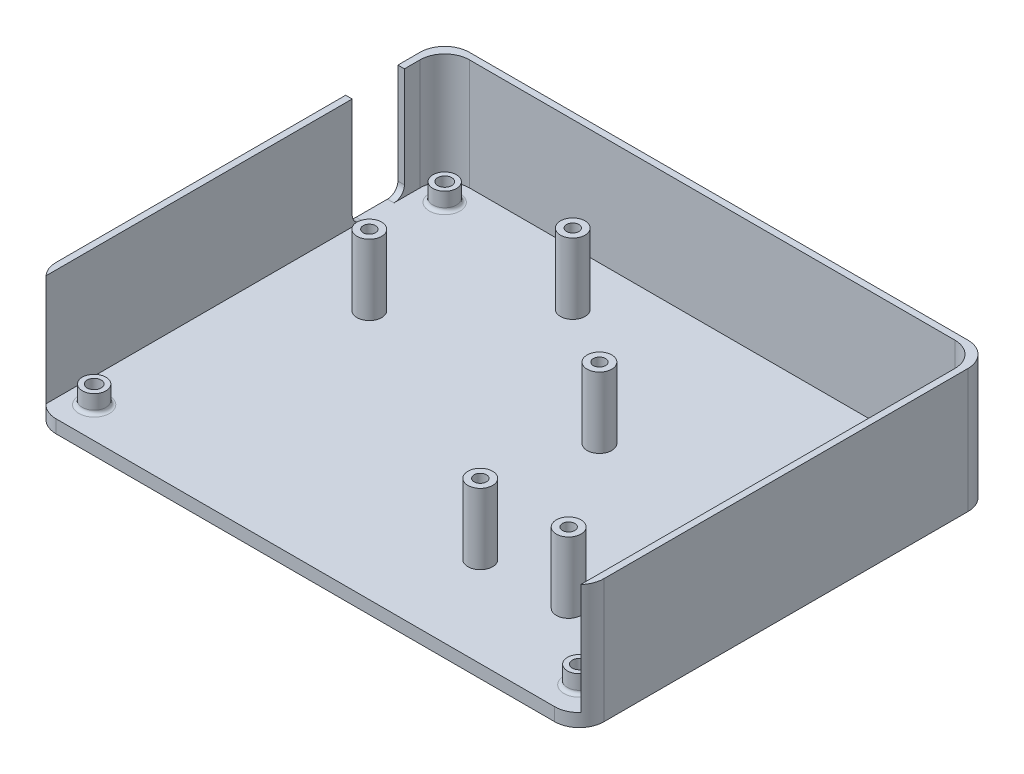
SolidWorks part; units mm, degrees
ref_plane "Front Plane" through (0, 0, 0) normal (0, 0, 1) x (1, 0, 0)
ref_plane "Top Plane" through (0, 0, 0) normal (0, 1, 0) x (1, 0, 0)
ref_plane "Right Plane" through (0, 0, 0) normal (1, 0, 0) x (0, 0, -1)
sketch "Sketch1" plane through (0, 0, 0) normal (0, 1, 0) x (1, 0, 0)
  line L0 (-66.8583, -50.2762) -> (-65.2708, -50.2762)
  line L1 (-65.2708, -50.2762) -> (64.8554, -50.2762)
  line L2 (-66.8583, -50.2762) -> (-66.8583, 44.2663)
  line L3 (-60.8583, 50.2663) -> (60.4429, 50.2663)
  line L4 (66.4429, -50.2762) -> (66.4429, 44.2663)
  line L5 (66.4429, -50.2762) -> (64.8554, -50.2762)
  line L6 (-50.3864, 41.1329) -> (-50.3864, 5.0649)
  line L7 (-50.3483, 41.1463) -> (49.9329, 41.1463)
  line L8 (-65.2708, -50.2762) -> (-65.2708, 42.6788)
  line L9 (-59.2708, 48.6788) -> (58.8554, 48.6788)
  line L10 (64.8554, -50.2762) -> (64.8554, 42.6788)
  line L11 (-50.3483, 41.1463) -> (-50.3483, -40.1162)
  line L12 (-50.3483, -40.1162) -> (49.9329, -40.1162)
  line L13 (49.9329, 41.1463) -> (49.9329, -40.1162)
  line L14 (-50.3864, 5.0649) -> (14.3836, 5.0649)
  line L15 (14.3836, 5.0649) -> (14.3836, -33.7971)
  line L16 (14.3836, -33.7971) -> (47.4036, -33.7971)
  line L17 (47.4036, -33.7971) -> (47.4036, 41.1329)
  line L18 (47.4036, 41.1329) -> (-50.3864, 41.1329)
  circle A0 centre (-59.2383, 42.6463) radius 1.7
  circle A1 centre (-59.2383, 42.6463) radius 2.875
  circle A2 centre (58.8229, 42.6463) radius 2.875
  circle A3 centre (58.8229, 42.6463) radius 1.7
  circle A4 centre (-59.2383, -42.6562) radius 2.875
  circle A5 centre (-59.2383, -42.6562) radius 1.7
  circle A6 centre (58.8229, -42.6562) radius 2.875
  circle A7 centre (58.8229, -42.6562) radius 1.7
  circle A8 centre (-21.0872, 35.6529) radius 1.5
  circle A9 centre (20.4128, -28.3471) radius 1.5
  circle A10 centre (-45.5872, 10.6529) radius 1.5
  circle A11 centre (10.4128, 10.6529) radius 1.5
  circle A12 centre (41.4128, -27.8471) radius 1.5
  arc A13 (-66.8583, 44.2663) -> (-60.8583, 50.2663) centre (-60.8583, 44.2663) cw
  arc A14 (-65.2708, 42.6788) -> (-59.2708, 48.6788) centre (-59.2708, 42.6788) cw
  circle A15 centre (-48.0512, -37.8237) radius 2
  arc A16 (58.8554, 48.6788) -> (64.8554, 42.6788) centre (58.8554, 42.6788) cw
  arc A17 (60.4429, 50.2663) -> (66.4429, 44.2663) centre (60.4429, 44.2663) cw
  circle A18 centre (-45.5872, 10.6529) radius 3
  circle A19 centre (-21.0872, 35.6529) radius 3
  circle A20 centre (10.4128, 10.6529) radius 3
  circle A21 centre (20.4128, -28.3471) radius 3
  circle A22 centre (41.4128, -27.8471) radius 3
  point P0 (0, 0)
  point P44 (-66.8583, 50.2663)
  point P53 (66.4429, 50.2663)
  dimension "D5" = 7.62
  dimension "D7" = 7.62
  dimension "D18" = 97.79
  dimension "D20" = 64.77
  dimension "D26" = 24.5
  dimension "D32" = 6
  dimension "D33" = 6
  dimension "D34" = 6
  dimension "D1" = 133.3013
  dimension "D2" = 100.5425
  dimension "D3" = 1.5875
  dimension "D4" = 1.5875
  dimension "D6" = 7.62
  dimension "D8" = 7.62
  dimension "D9" = 7.62
  dimension "D10" = 7.62
  dimension "D11" = 7.62
  dimension "D12" = 7.62
  dimension "D13" = 1.5875
  dimension "D14" = 9.12
  dimension "D15" = 16.51
  dimension "D16" = 16.51
  dimension "D17" = 81.2625
  dimension "D19" = 36.068
  dimension "D21" = 74.93
  dimension "D22" = 5.588
  dimension "D23" = 5.588
  dimension "D24" = 7.366
  dimension "D25" = 56
  dimension "D27" = 25
  dimension "D28" = 10
  dimension "D29" = 21
  dimension "D30" = 39
  dimension "D31" = 0.5
extrude "Boss-Extrude12" add sketch "Sketch1" along normal blind 3.175 contours L5 L4 A17 L3 A13 L2 L0 L1
extrude "Boss-Extrude13" add sketch "Sketch1<23>" along normal blind 30.1625 contours L10 L5 L4 L3 L2 L0 L8 L9 region at (-66.6913, 0, 3.005)
sketch "Sketch1<23>" plane through (0, 0, 0) normal (0, 1, 0) x (1, 0, 0) same geometry as "Sketch1"
extrude "Boss-Extrude15" add sketch "Sketch1<25>" along normal blind 7.525 contours A1 A0 | A2 A3 | A6 A7 | A4 A5 region at (-62.032, 0, -42.6463) region at (56.0293, 0, -42.6463) region at (-62.032, 0, 42.6562) region at (56.0293, 0, 42.6562)
sketch "Sketch1<25>" plane through (0, 0, 0) normal (0, 1, 0) x (1, 0, 0) same geometry as "Sketch1"
extrude "Cut-Extrude3" cut sketch "Sketch1<27>" along normal blind 28.575 contours A5 | A5 | A0 | A3 | A7 region at (-59.2383, 0, 42.6562)
sketch "Sketch1<27>" plane through (0, 0, 0) normal (0, 1, 0) x (1, 0, 0) same geometry as "Sketch1"
chamfer "Chamfer2" distance 1.45 angle 45 4 edges at (58.8229, 0, 44.3562) (58.8229, 0, -40.9463) (-59.2383, 0, 44.3562) (-59.2383, 0, -40.9463)
fillet "Fillet3" radius 6 2 edges at (66.4429, 15.0812, 50.2762) (-66.8583, 15.0812, 50.2762)
fillet "Fillet4" radius 0.85 1 edges at (-59.2383, 3.175, -45.5213)
fillet "Fillet5" radius 0.85 3 edges at (-59.2383, 3.175, 39.7812) (58.8229, 3.175, 39.7812) (58.8229, 3.175, -45.5213)
sketch "Sketch2" plane through (-65.2708, 0, 0) normal (1, 0, 0) x (0, 0, -1)
  line L0 (-48.3419, 3.175) -> (42.6788, 3.175) construction
  line L1 (38.8698, 3.175) -> (26.1698, 3.175)
  line L2 (38.8698, 3.175) -> (38.8698, 30.1625)
  line L3 (38.8698, 30.1625) -> (26.1698, 30.1625)
  line L4 (26.1698, 3.175) -> (26.1698, 30.1625)
  line L5 (-48.3419, 30.1625) -> (42.6788, 30.1625) construction
  line L6 (42.6788, 30.1625) -> (42.6788, 3.175) construction
  dimension "D1" = 12.7
  dimension "D2" = 3.8089
extrude "Cut-Extrude4" cut sketch "Sketch2" against normal blind 2.54
fillet "Fillet6" radius 2.54 2 edges at (-66.0646, 3.175, -38.8698) (-66.0646, 3.175, -26.1698)
extrude "Boss-Extrude16" add sketch "Sketch1<30>" along normal blind 20.32 contours A18 A10 | A19 A8 | A20 A11 | A22 A12 | A21 A9 region at (-48.5024, 0, -10.6529) region at (-24.0024, 0, -35.6529) region at (7.4976, 0, -10.6529) region at (17.4976, 0, 28.3471) region at (38.4976, 0, 27.8471)
sketch "Sketch1<30>" plane through (0, 0, 0) normal (0, 1, 0) x (1, 0, 0) same geometry as "Sketch1"
